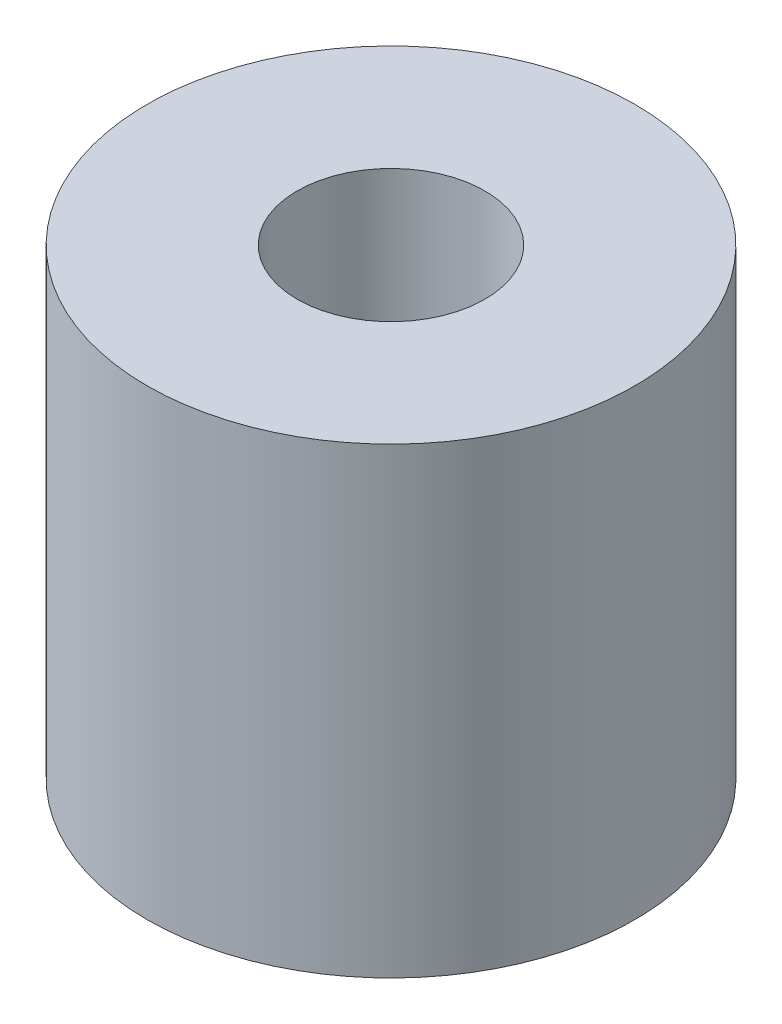
SolidWorks part; units mm, degrees
ref_plane "Front Plane" through (0, 0, 0) normal (0, 0, 1) x (1, 0, 0)
ref_plane "Top Plane" through (0, 0, 0) normal (0, 1, 0) x (1, 0, 0)
ref_plane "Right Plane" through (0, 0, 0) normal (1, 0, 0) x (0, 0, -1)
sketch "Sketch1" plane through (0, 0, 0) normal (0, 1, 0) x (1, 0, 0)
  circle A0 centre (0, 0) radius 5
  circle A1 centre (0, 0) radius 1.575
  dimension "D1" = 10
  dimension "D2" = 3.15
extrude "Boss-Extrude1" add sketch "Sketch1" along normal blind 9.48
sketch "Sketch2" plane through (0, 9.48, 0) normal (0, 1, 0) x (1, 0, 0)
  circle A0 centre (0, 0) radius 1.925
  circle M2 centre (0, 0) radius 1.575
  dimension "D1" = 3.85
extrude "Cut-Extrude1" cut sketch "Sketch2" against normal blind 4 contours M2 region at (-1.8706, 9.48, 0)
equation "\"bearing_21_OD\"= 21mm"
equation "\"pin_cirlce_diameter\"= 75mm"
equation "\"pin_diam\"= 6mm"
equation "\"gear_thickness\"= 4mm"
equation "\"ball_bearing_diam\"= 2.96mm"
equation "\"bearing_21_outer_clearance\"= 0.127mm'change this"
equation "\"bearing_15_OD\"= 15mm"
equation "\"bearing_15_outer_clearance\"= 0mm'change this"
equation "\"thrust_bearing_thickness\"= 5mm'measure this irl and change"
equation "\"D1@Boss-Extrude1\"=\"gear_thickness\"*2+0.5*\"ball_bearing_diam\""
